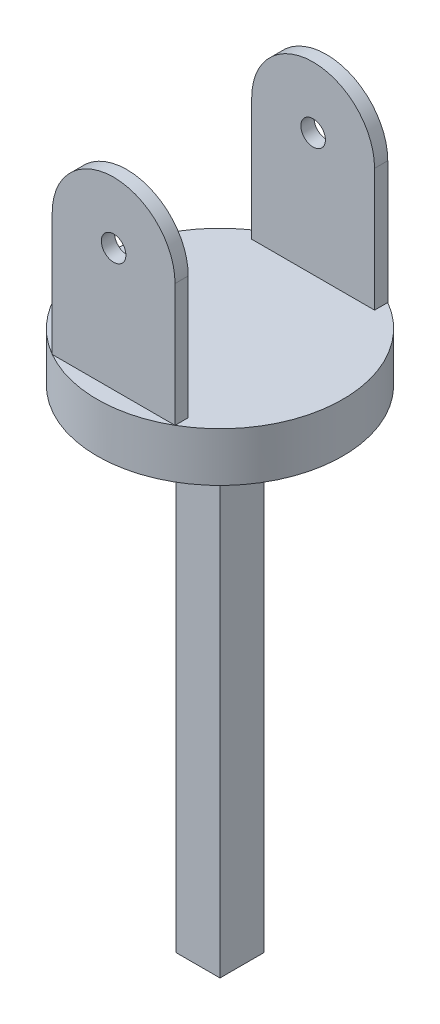
SolidWorks part; units mm, degrees
ref_plane "Front Plane" through (0, 0, 0) normal (0, 0, 1) x (1, 0, 0)
ref_plane "Top Plane" through (0, 0, 0) normal (0, 1, 0) x (1, 0, 0)
ref_plane "Right Plane" through (0, 0, 0) normal (1, 0, 0) x (0, 0, -1)
sketch "Sketch2" plane through (0, 0, 0) normal (0, 1, 0) x (1, 0, 0)
  line L1 (-1.8, -1.8) -> (1.8, -1.8)
  line L2 (-1.8, -1.8) -> (-1.8, 1.8)
  line L3 (-1.8, 1.8) -> (1.8, 1.8)
  line L4 (1.8, -1.8) -> (1.8, 1.8)
  line L5 (-1.8, -1.8) -> (1.8, 1.8) construction
  line L6 (-1.8, 1.8) -> (1.8, -1.8) construction
  point P0 (0, 0)
  dimension "D1" = 3.6
  dimension "D2" = 3.6
extrude "Boss-Extrude1" add sketch "Sketch2" along normal blind 40
sketch "Sketch3" plane through (0, 40, 0) normal (0, 1, 0) x (1, 0, 0)
  circle A0 centre (0, 0) radius 10
  dimension "D1" = 20
extrude "Boss-Extrude2" add sketch "Sketch3" along normal blind 4
sketch "Sketch5" plane through (0, 44, 0) normal (0, 1, 0) x (1, 0, 0)
  line L0 (-5, 8.6603) -> (5, 8.6603)
  line L1 (-5, 8.6603) -> (-5, 7.5849)
  line L2 (5, 8.6603) -> (5, 7.5849)
  line L3 (-5, 7.5849) -> (5, 7.5849)
  line L4 (0, 0) -> (5, 0) construction
  line L5 (5, -8.6603) -> (5, -7.5849)
  line L6 (-5, -7.5849) -> (5, -7.5849)
  line L7 (-5, -8.6603) -> (-5, -7.5849)
  line L8 (-5, -8.6603) -> (5, -8.6603)
  circle A0 centre (0, 0) radius 10 construction
  dimension "D1" = 10
  dimension "D2" = 1.0754
  dimension "D3" = 0
extrude "Boss-Extrude3" add sketch "Sketch5" along normal blind 15
fillet "Fillet3" 2 edges at (-5, 59, 8.1226) (5, 59, 8.1226) type full round first side face at (-5, 51.5, 8.1226) second side face at (5, 51.5, 8.1226) middle face at (0, 59, 8.1226)
fillet "Fillet4" 2 edges at (-5, 59, -8.1226) (5, 59, -8.1226) type full round first side face at (-5, 51.5, -8.1226) second side face at (5, 51.5, -8.1226) middle face at (0, 59, -8.1226)
sketch "Sketch6" plane through (0, 0, 8.6603) normal (0, 0, 1) x (1, 0, 0)
  circle A0 centre (0, 54) radius 1
  dimension "D1" = 2
extrude "Cut-Extrude1" cut sketch "Sketch6" against normal up to surface (17.3205 mm away) up to face at (0, 50.25, -8.6603)
